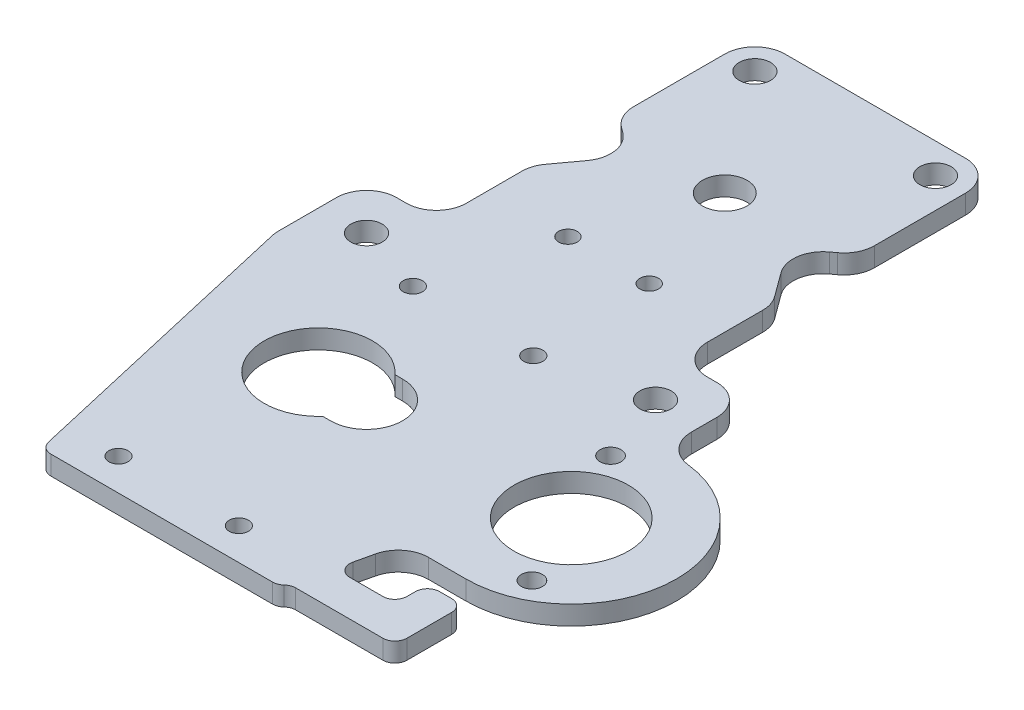
SolidWorks part; units mm, degrees
material "6061-T6 (SS)"
ref_plane "Front Plane" through (0, 0, 0) normal (0, 0, 1) x (1, 0, 0)
ref_plane "Top Plane" through (0, 0, 0) normal (0, 1, 0) x (1, 0, 0)
ref_plane "Right Plane" through (0, 0, 0) normal (1, 0, 0) x (0, 0, -1)
sketch "Sketch1" plane through (0, 0, 0) normal (0, 1, 0) x (1, 0, 0)
  line L0 (0, -93.5) -> (0, 0) construction
  line L1 (-20, -12.0684) -> (-7.2598, 5.3193)
  line L2 (0, -53.5) -> (-1.2918, -53.5)
  line L3 (-31.6, -43.1) -> (-20, -93.5)
  line L4 (34, -77) -> (23.7976, -77)
  line L5 (0, -65.5) -> (-1.2918, -65.5)
  line L6 (-24, -35.5) -> (24, -35.5) construction
  line L7 (23.7976, -77) -> (20, -93.5)
  line L8 (20, -27.9) -> (31.6, -27.9)
  line L9 (-2.5, -39.3) -> (-2.5, -88.2) construction
  line L10 (7.5, -88.2) -> (-12.5, -88.2) construction
  line L11 (-31.6, -43.1) -> (-31.6, -27.9)
  line L12 (31.6, -42.1654) -> (31.6, -27.9)
  line L13 (7.5, -88.2) -> (7.5, -39.3) construction
  line L14 (-20, -12.0684) -> (-20, -27.9)
  line L15 (-20, -27.9) -> (-31.6, -27.9)
  line L16 (20, -12.0684) -> (20, -27.9)
  line L17 (20, -12.0684) -> (7.2598, 5.3193)
  line L18 (7.5, -39.3) -> (-12.5, -39.3) construction
  line L19 (-12.5, -88.2) -> (-12.5, -39.3) construction
  line L20 (7.5, -88.2) -> (-12.5, -39.3) construction
  line L21 (7.5, -39.3) -> (-12.5, -88.2) construction
  line L22 (7.5, -63.75) -> (-12.5, -63.75) construction
  line L23 (40.4449, -73.3212) -> (41.3958, -75.3604) construction
  line L25 (40.4449, -73.3212) -> (38.9658, -70.1491) construction
  line L26 (38.0149, -68.1099) -> (34, -59.5) construction
  line L27 (34, -59.5) -> (28.2947, -47.2648) construction
  line L28 (38.0149, -68.1099) -> (38.9658, -70.1491) construction
  line L30 (-20, -93.5) -> (20, -93.5)
  circle A0 centre (34, -59.5) radius 9.5
  arc A1 (34, -77) -> (31.6, -42.1654) centre (34, -59.5) ccw
  arc A2 (-1.2918, -53.5) -> (-1.2918, -65.5) centre (-8, -59.5) ccw
  circle A3 centre (28.2947, -47.2648) radius 1.75
  circle A4 centre (39.7053, -71.7352) radius 1.75
  circle A5 centre (-24, -35.5) radius 2.6
  circle A6 centre (24, -35.5) radius 2.6
  circle A7 centre (0, 0) radius 3.7
  circle A8 centre (-12.5, -39.3) radius 1.6
  circle A9 centre (-6.75, -19.3) radius 1.55
  circle A10 centre (6.75, -19.3) radius 1.55
  circle A11 centre (7.5, -39.3) radius 1.6
  circle A12 centre (7.5, -88.2) radius 1.6
  circle A13 centre (-12.5, -88.2) radius 1.6
  circle A14 centre (34, -59.5) radius 13.5 construction
  arc A15 (0, -65.5) -> (0, -53.5) centre (0, -59.5) ccw
  arc A16 (7.2598, 5.3193) -> (-7.2598, 5.3193) centre (0, 0) ccw
  point P2 (-2.5, -63.75)
  point P22 (43.5, -59.5)
  point P29 (51.5, -59.5)
  point P35 (38.0149, -68.1099)
  point P37 (38.9658, -70.1491)
  point P38 (40.4449, -73.3212)
  dimension "D4" = 18
  dimension "D6" = 16.2
  dimension "D7" = 13.5
  dimension "D8" = 7.6
  dimension "D9" = 48
  dimension "D10" = 8
  dimension "D11" = 12
  dimension "D12" = 40
  dimension "D13" = 7.4
  dimension "D14" = 40
  dimension "D15" = 3.1
  dimension "D16" = 5.2
  dimension "D19" = 3.2
  dimension "D20" = 19
  dimension "D21" = 34
  dimension "D22" = 24
  dimension "D23" = 48.9
  dimension "D24" = 20
  dimension "D25" = 8
  dimension "D17" = 9
  dimension "D18" = 7.6
  dimension "D3" = 35.5
  dimension "D5" = 65
  dimension "D26" = 20.2
  dimension "D27" = 3.5
  dimension "D28" = 12.5
  dimension "D32" = 34
extrude "Boss-Extrude1" add sketch "Sketch1" along normal blind 3.175
sketch "Sketch2" plane through (0, 3.175, 0) normal (0, 1, 0) x (1, 0, 0)
  line L0 (-24, -35.5) -> (24, -35.5) construction
fillet "Fillet1" radius 5 9 edges at (31.6, 1.5875, 27.9) (20, 1.5875, 27.9) (20, 1.5875, 12.0684) (-20, 1.5875, 12.0684) (-20, 1.5875, 27.9) (-31.6, 1.5875, 27.9) (-31.6, 1.5875, 43.1) (31.6, 1.5875, 42.1654) (23.7976, 1.5875, 77)
fillet "Fillet2" radius 2 2 edges at (20, 1.5875, 93.5) (-20, 1.5875, 93.5)
sketch "Sketch3" plane through (0, 3.175, 0) normal (0, 1, 0) x (1, 0, 0)
  line L0 (21.631, -86.4136) -> (31.631, -86.4136)
  line L1 (20.3571, -91.9486) -> (22.9049, -80.8785) construction
  line L2 (31.631, -86.4136) -> (31.631, -81)
  line L3 (31.631, -81) -> (37.631, -81)
  line L4 (37.631, -81) -> (37.631, -92.4136)
  line L5 (37.631, -92.4136) -> (20.2501, -92.4136)
  line L6 (21.631, -86.4136) -> (20.2501, -92.4136)
  line L7 (27.7775, -77) -> (34, -77) construction
  dimension "D1" = 4
  dimension "D2" = 6
  dimension "D3" = 10
  dimension "D4" = 6
extrude "Boss-Extrude2" add sketch "Sketch3" against normal up to surface (3.175 mm away) up to face at (-6.75, 0, 20.85)
fillet "Fillet3" radius 2 5 edges at (37.631, 1.5875, 92.4136) (31.631, 1.5875, 86.4136) (37.631, 1.5875, 81) (31.631, 1.5875, 81) (21.631, 1.5875, 86.4136)
fillet "Fillet4" radius 2 4 edges at (20.3571, 1.5875, 91.9486) (20.2501, 1.5875, 92.4136) (20.3036, 3.175, 92.1811) (20.3036, 0, 92.1811)
sketch "Sketch4" plane through (0, 3.175, 0) normal (0, 1, 0) x (1, 0, 0)
  line L0 (19.0332, -10.7489) -> (7.2598, 5.3193) construction
  line L1 (-7.2598, 5.3193) -> (-19.0332, -10.7489) construction
  line L2 (13.1465, -2.7148) -> (7.2598, 5.3193)
  line L3 (-7.2598, 5.3193) -> (-13.1465, -2.7148)
  line L4 (-13.1465, -2.7148) -> (-20, 2.3068)
  line L5 (-20, 2.3068) -> (-20, 25)
  line L6 (-20, 25) -> (20, 25)
  line L7 (0, 25) -> (0, 0) construction
  line L8 (13.1465, -2.7148) -> (20, 2.3068)
  line L9 (20, 2.3068) -> (20, 25)
  arc A0 (7.2598, 5.3193) -> (-7.2598, 5.3193) centre (0, 0) ccw construction
  arc A1 (7.2598, 5.3193) -> (-7.2598, 5.3193) centre (0, 0) ccw
  circle A2 centre (-15, 20) radius 2.6
  circle A3 centre (0, 0) radius 3.7 construction
  circle A4 centre (15, 20) radius 2.6
  dimension "D1" = 5.2
  dimension "D2" = 5
  dimension "D3" = 5
  dimension "D4" = 30
  dimension "D5" = 25
extrude "Boss-Extrude3" add sketch "Sketch4" against normal up to surface (3.175 mm away) up to face at (12.3322, 0, 54.891)
fillet "Fillet5" radius 5 6 edges at (13.1465, 1.5875, 2.7148) (-13.1465, 1.5875, 2.7148) (-20, 1.5875, -2.3068) (20, 1.5875, -2.3068) (20, 1.5875, -25) (-20, 1.5875, -25)
